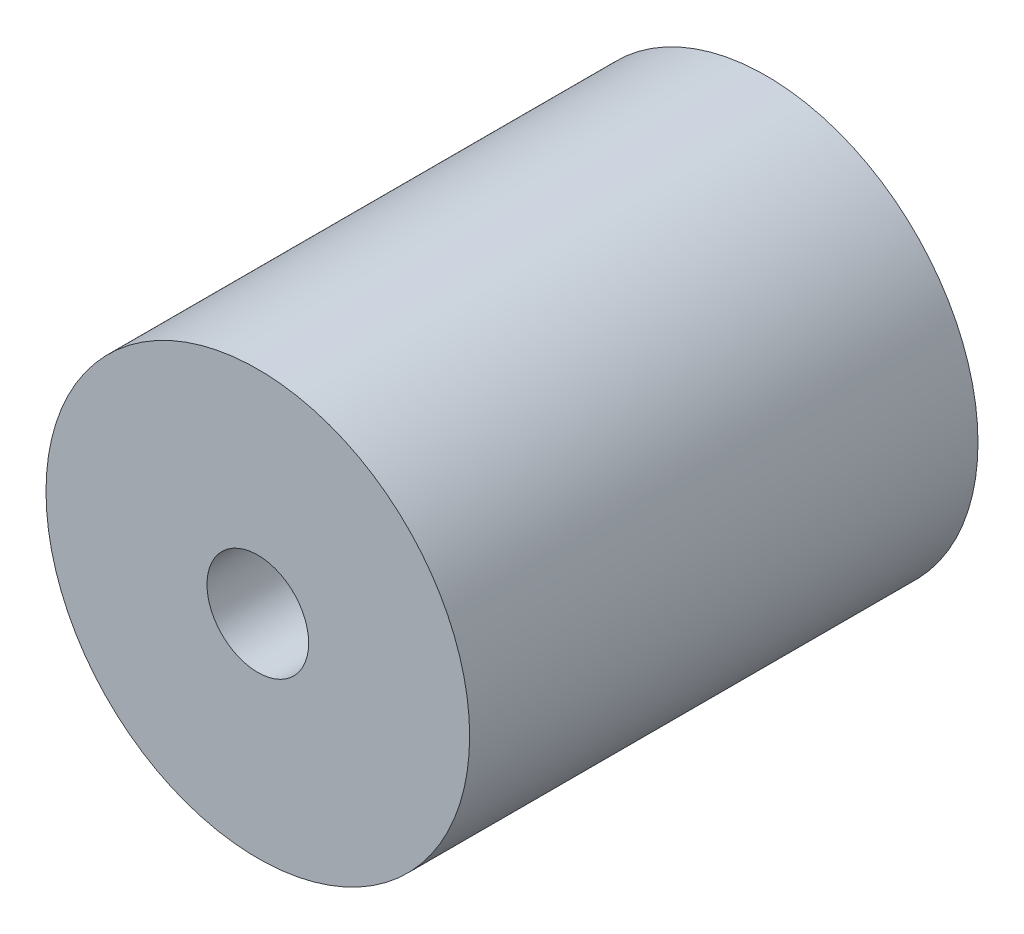
SolidWorks part; units mm, degrees
ref_plane "Front Plane" through (0, 0, 0) normal (0, 0, 1) x (1, 0, 0)
ref_plane "Top Plane" through (0, 0, 0) normal (0, 1, 0) x (1, 0, 0)
ref_plane "Right Plane" through (0, 0, 0) normal (1, 0, 0) x (0, 0, -1)
sketch "Sketch1" plane through (0, 0, 0) normal (0, 0, 1) x (1, 0, 0)
  circle A0 centre (0, 0) radius 15.875
  circle A1 centre (0, 0) radius 3.81
  dimension "D1" = 31.75
  dimension "D2" = 7.62
extrude "Boss-Extrude1" add sketch "Sketch1" along normal blind 19.05 and the other way blind 19.05
